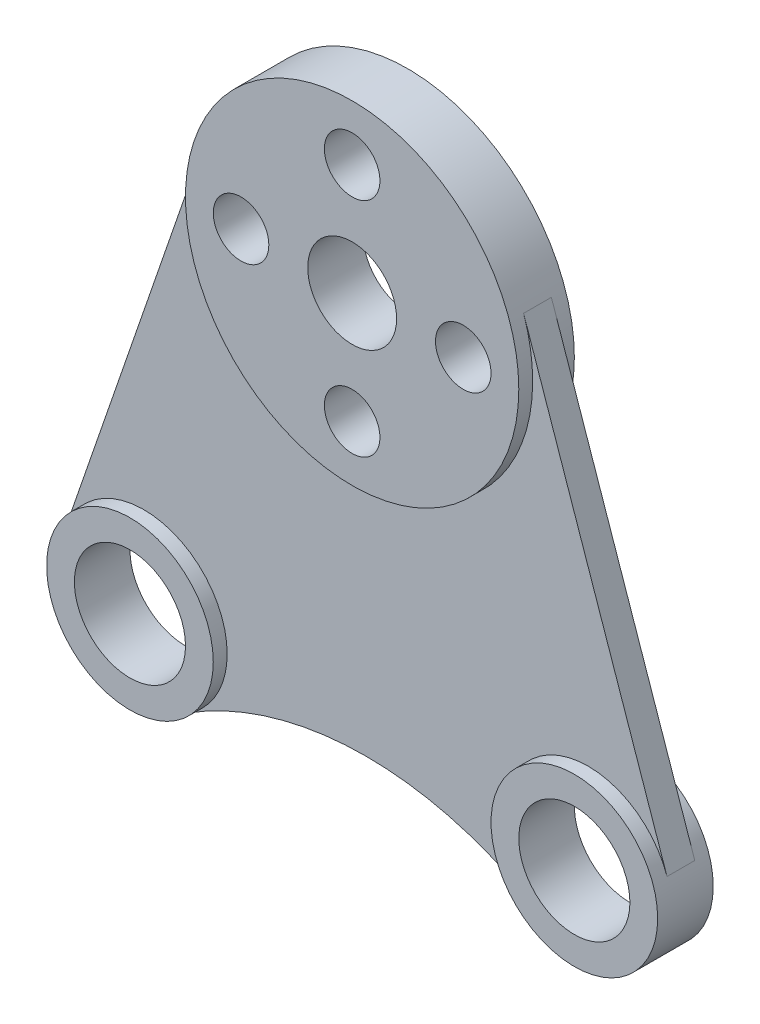
SolidWorks part; units mm, degrees
ref_plane "Front Plane" through (0, 0, 0) normal (0, 0, 1) x (1, 0, 0)
ref_plane "Top Plane" through (0, 0, 0) normal (0, 1, 0) x (1, 0, 0)
ref_plane "Right Plane" through (0, 0, 0) normal (1, 0, 0) x (0, 0, -1)
sketch "Sketch1" plane through (0, 0, 0) normal (0, 0, 1) x (1, 0, 0)
  line L0 (-54.1809, -65.1109) -> (-28.3617, 9.7781)
  line L1 (0, 0) -> (0, -65.1109) construction
  line L2 (54.1809, -65.1109) -> (28.3617, 9.7781)
  circle A0 centre (0, 0) radius 20 construction
  circle A1 centre (0, 0) radius 30
  circle A2 centre (0, 0) radius 8
  circle A3 centre (0, 20) radius 5
  circle A4 centre (20, 0) radius 5
  circle A5 centre (0, -20) radius 5
  circle A6 centre (-20, 0) radius 5
  circle A7 centre (-40, -70) radius 10
  circle A8 centre (-40, -70) radius 15
  circle A9 centre (40, -70) radius 15
  circle A10 centre (40, -70) radius 10
  arc A11 (-32, -82.6886) -> (32, -82.6886) centre (0, -133.4429) cw
  point P16 (0, 0)
  point P28 (0, 0)
  point P29 (0, 0)
  dimension "D1" = 40
  dimension "D2" = 60
  dimension "D3" = 16
  dimension "D4" = 10
  dimension "D6" = 20
  dimension "D7" = 30
  dimension "D8" = 70
  dimension "D9" = 40
  dimension "D10" = 60
  dimension "D5" = 4
extrude "Boss-Extrude1" add sketch "Sketch1" along normal mid plane 10 contours A1 A6 A5 A4 A3 A2 | A8 A7 | A9 A10 region at (-37.5915, -55.6246, 0) region at (0, 29.1515, 0) region at (30.9472, -58.5764, 0)
extrude "Boss-Extrude2" add sketch "Sketch1<3>" along normal mid plane 5 contours A8 A11 A9 L2 A1 L0 region at (0, -44.6055, 0)
sketch "Sketch1<3>" plane through (0, 0, 0) normal (0, 0, 1) x (1, 0, 0) same geometry as "Sketch1"
